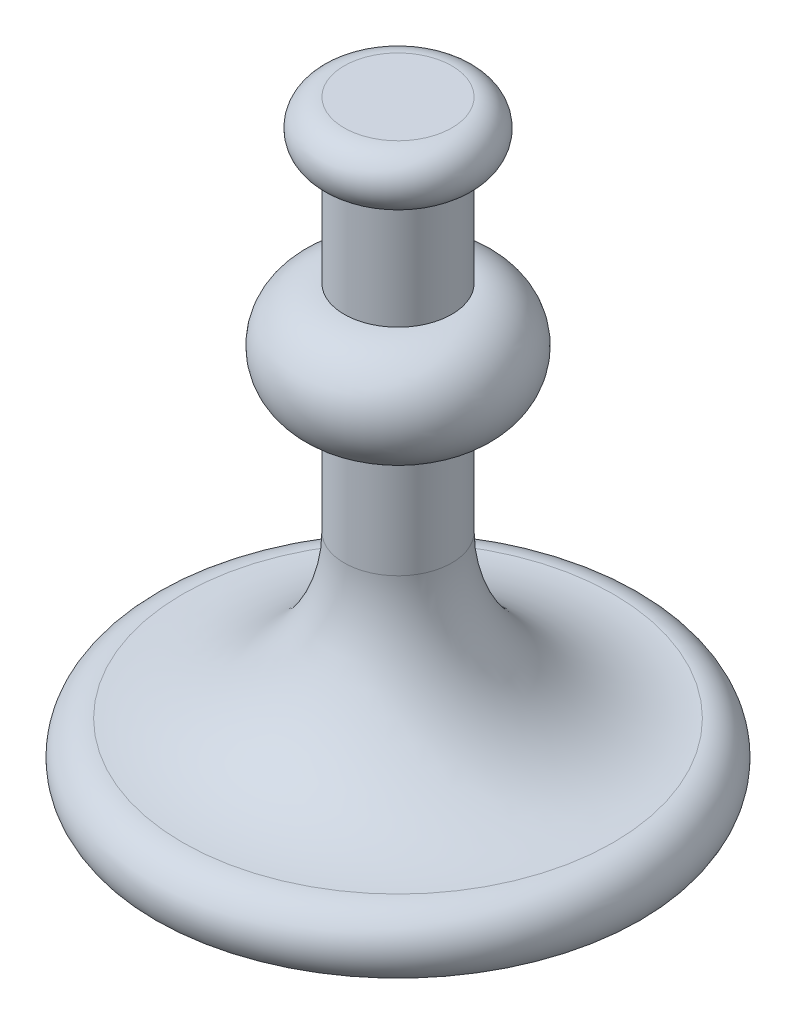
SolidWorks part; units mm, degrees
ref_plane "Front Plane" through (0, 0, 0) normal (0, 0, 1) x (1, 0, 0)
ref_plane "Top Plane" through (0, 0, 0) normal (0, 1, 0) x (1, 0, 0)
ref_plane "Right Plane" through (0, 0, 0) normal (1, 0, 0) x (0, 0, -1)
sketch "Sketch2" plane through (0, 0, 0) normal (0, 0, 1) x (1, 0, 0)
  line L0 (0, 0) -> (0, 220)
  line L1 (0, 220) -> (20, 220)
  line L2 (0, 0) -> (90, 0)
  line L3 (20, 200) -> (20, 160)
  line L4 (20, 120) -> (20, 80)
  arc A0 (20, 220) -> (20, 200) centre (20, 210) cw
  arc A1 (20, 160) -> (20, 120) centre (20, 140) cw
  arc A2 (20, 80) -> (80, 20) centre (80, 80) ccw
  arc A3 (80, 20) -> (90, 0) centre (80, 7.5) cw
  dimension "D4" = 10
  dimension "D5" = 20
  dimension "D7" = 60
  dimension "D8" = 12.5
  dimension "D1" = 20
  dimension "D2" = 220
  dimension "D3" = 90
  dimension "D6" = 40
  dimension "D9" = 80
revolve "Revolve1" add sketch "Sketch2" angle 360 about L0
sketch "Sketch4" plane through (0, 0, 0) normal (0, 0, 1) x (1, 0, 0)
  line L0 (0, 10) -> (60, 10)
  line L1 (0, 227.4356) -> (0, 175.1288) construction
  line L2 (-90, 0) -> (90, 0) construction
  arc A0 (60, 10) -> (183.5921, 75) centre (60, 160) ccw
  arc A1 (183.5921, 75) -> (150.6342, 75) centre (167.1131, 86.3333) ccw
  point P8 (0, 0)
  point P9 (0, 0)
  point P12 (0, 10)
  dimension "D1" = 150
  dimension "D3" = 20
  dimension "D2" = 65
  dimension "D4" = 60
  dimension "D5" = 32.9579
  dimension "D6" = 10
sketch "Sketch5" plane through (0, 0, 0) normal (1, 0, 0) x (0, 0, -1)
  ellipse E0 centre (0, 10) end of major axis (-17.5, 10) minor radius 5
  point P1 (0, 10)
  point P7 (0, 10)
  point P9 (0, 10)
  point P11 (0, 0)
  dimension "D1" = 10
  dimension "D2" = 35
